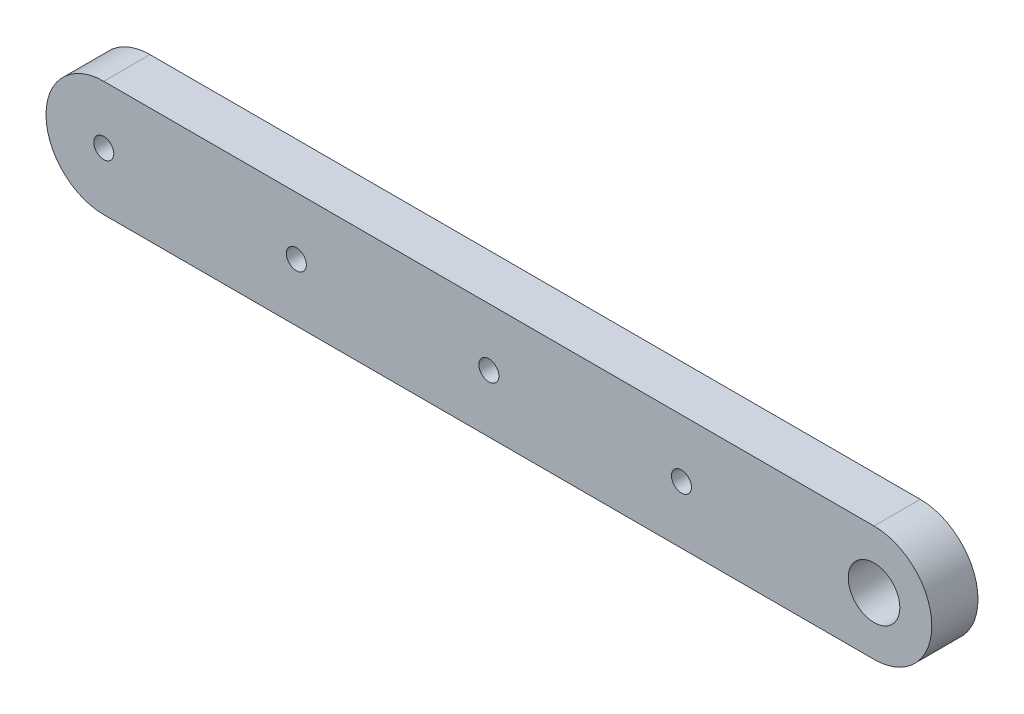
SolidWorks part; units mm, degrees
material "Pine"
ref_plane "Front Plane" through (0, 0, 0) normal (0, 0, 1) x (1, 0, 0)
ref_plane "Top Plane" through (0, 0, 0) normal (0, 1, 0) x (1, 0, 0)
ref_plane "Right Plane" through (0, 0, 0) normal (1, 0, 0) x (0, 0, -1)
sketch "Sketch1" plane through (0, 0, 0) normal (0, 0, 1) x (1, 0, 0)
  line L0 (0, 7.5) -> (100, 7.5)
  line L1 (100, -7.5) -> (0, -7.5)
  circle A0 centre (0, 0) radius 7.5
  circle A1 centre (100, 0) radius 7.5
  dimension "D1" = 100
  dimension "D2" = 15
extrude "Boss-Extrude1" add sketch "Sketch1" along normal blind 6 contours A1 L0 A0 L1 | A1 | A0 region at (50, 0, 0) region at (0, 0, 0) region at (100, 0, 0)
ref_plane "Plane1" through (0, 0, 3) normal (0, 0, 1) x (1, 0, 0)
sketch "Sketch2" plane through (0, 0, 6) normal (0, 0, 1) x (1, 0, 0)
  circle A0 centre (0, 0) radius 1.3
  circle A1 centre (100, 0) radius 1.3
  dimension "D1" = 2.6
extrude "Cut-Extrude1" cut sketch "Sketch2" against normal through all
pattern_linear "LPattern1" count 4 spacing 25 along (1, 0, 0) of "Cut-Extrude1"
sketch "Sketch3" plane through (0, 0, 6) normal (0, 0, 1) x (1, 0, 0)
  circle A0 centre (100, 0) radius 3.35
  dimension "D1" = 6.7
extrude "Cut-Extrude2" cut sketch "Sketch3" against normal through all
